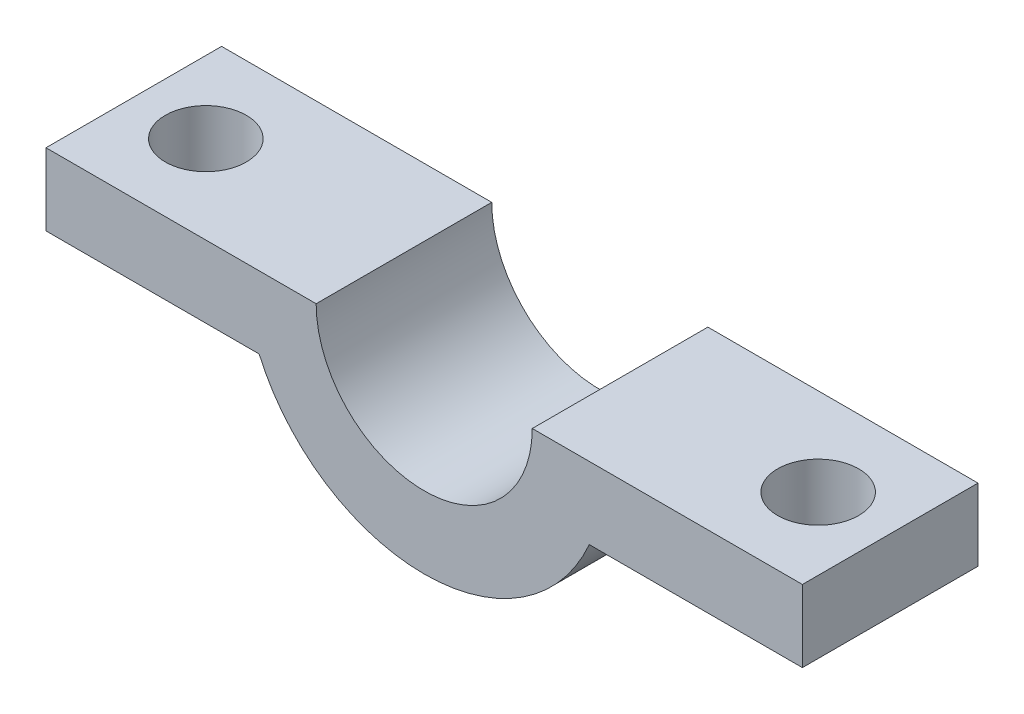
SolidWorks part; units mm, degrees
ref_plane "Front Plane" through (0, 0, 0) normal (0, 0, 1) x (1, 0, 0)
ref_plane "Top Plane" through (0, 0, 0) normal (0, 1, 0) x (1, 0, 0)
ref_plane "Right Plane" through (0, 0, 0) normal (1, 0, 0) x (0, 0, -1)
sketch "Sketch1" plane through (0, 0, 0) normal (0, 0, 1) x (1, 0, 0)
  arc A0 (-6, 0) -> (6, 0) centre (0, 0) ccw
extrude "Extrude-Thin1" add sketch "Sketch1" along normal blind 9.75 thin thin type one direction wall 4
sketch "Sketch3" plane through (0, 0, 0) normal (0, 1, 0) x (1, 0, 0)
  line L1 (-21, 0) -> (-6, 0)
  line L2 (-21, 0) -> (-21, -9.75)
  line L3 (-21, -9.75) -> (-6, -9.75)
  line L4 (21, 0) -> (21, -9.75)
  line L5 (6, -9.75) -> (10, -9.75) construction
  line L6 (6, 0) -> (10, 0) construction
  line L7 (-6, 0) -> (-6, -9.75)
  line L8 (6, 0) -> (6, -9.75)
  line L9 (6, 0) -> (21, 0)
  line L10 (6, -9.75) -> (21, -9.75)
  dimension "D1" = 42
extrude "Boss-Extrude1" add sketch "Sketch3" against normal blind 4
sketch "Sketch4" plane through (0, 0, 0) normal (0, 1, 0) x (1, 0, 0)
  line L0 (-21, 0) -> (-21, -9.75) construction
  line L1 (-21, 0) -> (-6, 0) construction
  line L2 (0, -5.3625) -> (0, 5.3625) construction
  circle A0 centre (-17, -4.875) radius 2.25
  circle A1 centre (17, -4.875) radius 2.25
  dimension "D2" = 4.875
  dimension "D1" = 4
extrude "Cut-Extrude1" cut sketch "Sketch4" against normal through all
